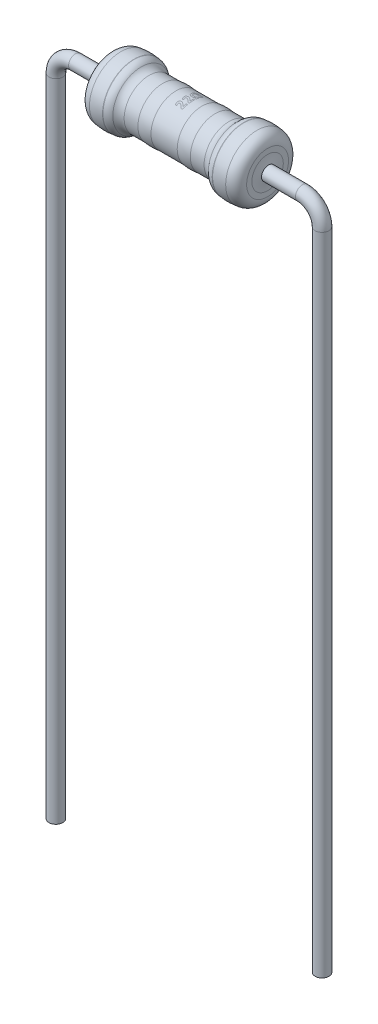
SolidWorks part; units mm, degrees
material "Plain Carbon Steel"
ref_plane "Front Plane" through (0, 0, 0) normal (0, 0, 1) x (1, 0, 0)
ref_plane "Top Plane" through (0, 0, 0) normal (0, 1, 0) x (1, 0, 0)
ref_plane "Right Plane" through (0, 0, 0) normal (1, 0, 0) x (0, 0, -1)
sketch "Sketch1" plane through (0, 0, 0) normal (0, 0, 1) x (1, 0, 0)
  line L0 (-4.33, 0) -> (4.33, 0)
  line L1 (-5.08, -0.75) -> (-5.08, -25.4)
  line L2 (5.08, -0.75) -> (5.08, -25.4)
  line L3 (-5.08, -25.4) -> (5.08, -25.4) construction
  line L4 (0, 0) -> (0, -25.4) construction
  arc A0 (-4.33, 0) -> (-5.08, -0.75) centre (-4.33, -0.75) ccw
  arc A1 (4.33, 0) -> (5.08, -0.75) centre (4.33, -0.75) cw
  dimension "D2" = 0.75
  dimension "D1" = 10.16
  dimension "D3" = 25.4
ref_plane "Plane1" through (-5.08, -25.4, 0) normal (0, -1, 0) x (-1, 0, 0)
sketch "Sketch2" plane through (-5.08, -25.4, 0) normal (0, -1, 0) x (-1, 0, 0)
  circle A0 centre (0, 0) radius 0.265
  dimension "D1" = 0.53
sweep "Sweep1" add profiles "Sketch2" path "Sketch1"
sketch "Sketch3" plane through (0, 0, 0) normal (0, 0, 1) x (1, 0, 0)
  line L0 (-3, 0) -> (3, 0)
  line L5 (-3, 0) -> (-3, 1.2)
  line L6 (3, 0) -> (3, 1.2)
  line L7 (-3, 1.2) -> (-1.75, 1.2)
  line L8 (3, 1.2) -> (1.75, 1.2)
  line L9 (-1.75, 1.2) -> (-1.75, 0.95)
  line L10 (-1.75, 0.95) -> (1.75, 0.95)
  line L11 (1.75, 0.95) -> (1.75, 1.2)
  line L12 (0, 0) -> (0, 0.95) construction
  dimension "D1" = 6
  dimension "D2" = 1.2
  dimension "D3" = 3.5
  dimension "D4" = 0.95
  dimension "D5" = 0.25
revolve "Revolve1" add sketch "Sketch3" angle 360 about L0
fillet "Fillet-1" radius 0.35 2 edges at (1.75, 0, 1.2) (-1.75, 0, 1.2)
fillet "Fillet-2" radius 0.4 4 edges at (3, 0, 1.2) (-3, 0, 1.2) (1.75, 0, 0.95) (-1.75, 0, 0.95)
sketch "Sketch5" plane through (0, 0, 0) normal (0, 0, 1) x (1, 0, 0)
  line L16 (-3, 0) -> (3, 0) construction
  line L17 (-2.6, 1.2) -> (-2.1, 1.2) construction
  line L18 (-2.6, 1.2) -> (-2.6, 0)
  line L19 (-2.6, 0) -> (-2.1, 0)
  line L20 (-2.1, 1.2) -> (-2.1, 0)
  line L21 (-1.75, 0.95) -> (1.75, 0.95) construction
  line L22 (2.6, 1.2) -> (2.1, 1.2) construction
  line L23 (2.6, 1.2) -> (2.6, 0)
  line L24 (2.6, 0) -> (2.1, 0)
  line L25 (2.1, 1.2) -> (2.1, 0)
  line L26 (-0.5, 0.95) -> (-1, 0.95) construction
  line L27 (-0.5, 0.95) -> (-0.5, 0)
  line L28 (-0.5, 0) -> (-1, 0)
  line L29 (-1, 0.95) -> (-1, 0)
  line L30 (-2.35, 1.2) -> (-2.35, 1.22) construction
  line L31 (1, 0.95) -> (0.5, 0.95) construction
  line L32 (1, 0.95) -> (1, 0)
  line L33 (1, 0) -> (0.5, 0)
  line L34 (0.5, 0.95) -> (0.5, 0)
  line L35 (-0.75, 0.95) -> (-0.75, 0.97) construction
  line L36 (0.75, 0.95) -> (0.75, 0.97) construction
  line L37 (2.35, 1.2) -> (2.35, 1.22) construction
  line L48 (-3, 0) -> (-3, 0.6)
  line L49 (-3, 0) -> (-3, 1.2) construction
  line L50 (-3, 0) -> (-3.05, 0)
  line L51 (-3.05, 0) -> (-3.05, 0.2)
  line L52 (3, 0) -> (3.05, 0)
  line L53 (3.05, 0) -> (3.05, 0.2)
  line L54 (3, 0) -> (3, 0.6)
  line L55 (3, 0) -> (3, 1.2) construction
  arc A0 (-2.6, 1.2) -> (-2.1, 1.2) centre (-2.35, -0.3525) cw
  arc A1 (-1, 0.95) -> (-0.5, 0.95) centre (-0.75, -0.6025) cw
  arc A2 (0.5, 0.95) -> (1, 0.95) centre (0.75, -0.6025) cw
  arc A3 (2.1, 1.2) -> (2.6, 1.2) centre (2.35, -0.3525) cw
  arc A6 (-3, 0.6) -> (-3.05, 0.2) centre (-4.625, 0.6) cw
  arc A7 (3.05, 0.2) -> (3, 0.6) centre (4.625, 0.6) cw
  dimension "D4" = 0.02
  dimension "D5" = 0.05
  dimension "D7" = 0.6
  dimension "D1" = 0.5
  dimension "D2" = 0.5
  dimension "D3" = 0.5
  dimension "D6" = 0.2
revolve "Revolve3" add sketch "Sketch5" angle 360 about L19
ref_plane "Plane2" through (0, 2, 0) normal (0, 1, 0) x (1, 0, 0)
sketch "Sketch6" plane through (0, 2, 0) normal (0, 1, 0) x (1, 0, 0)
  line L0 (0, 0) -> (0.15, 0) construction
  line L1 (0.15, 0.95) -> (0.15, -0.95) construction
  line L2 (0.5, 0.95) -> (-0.5, 0.95) construction
  text T0 "22Ω" font "Calibri" height 0.3
  dimension "D1" = 0.15
wrap "Wrap1" sketch "Sketch6" wrap type scribe source sketch "Sketch6" face at (-0.5, -0.95, 0)
